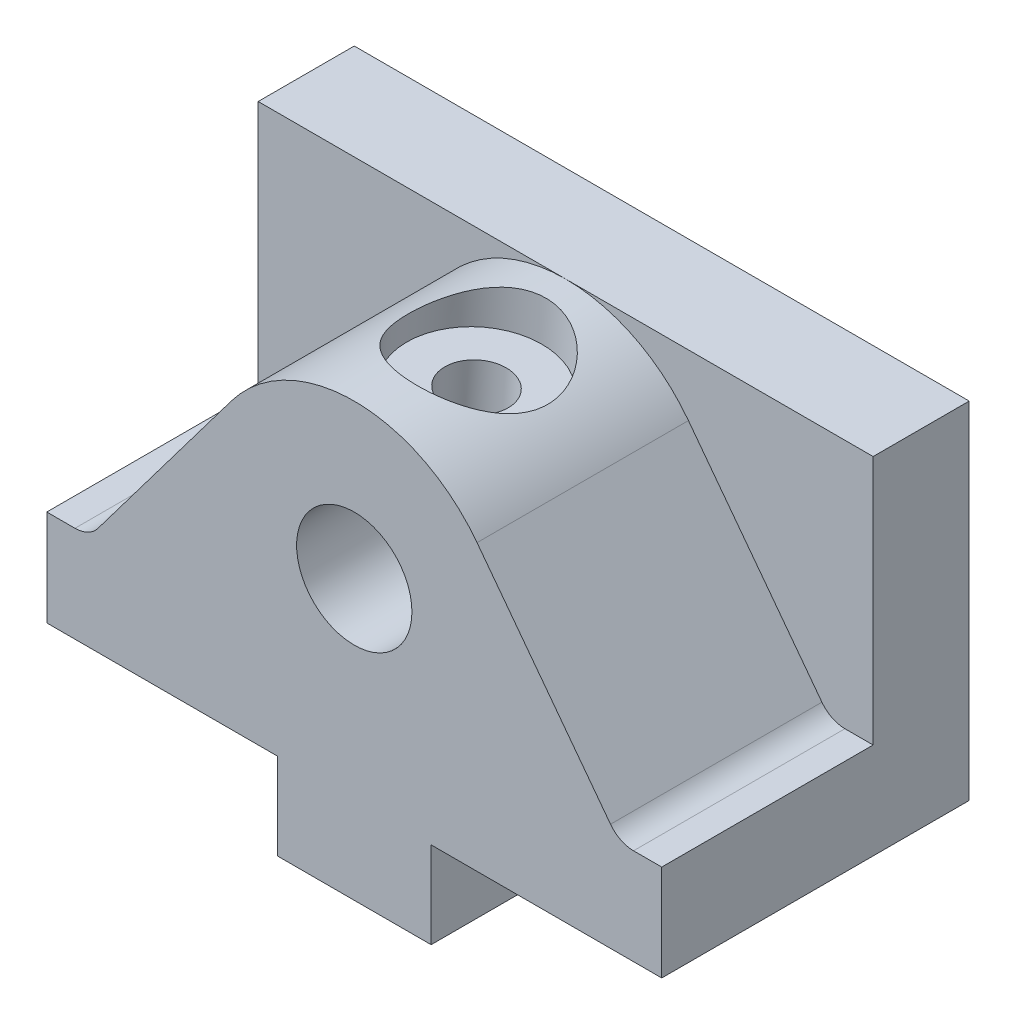
SolidWorks part; units mm, degrees
ref_plane "Front Plane" through (0, 0, 0) normal (0, 0, 1) x (1, 0, 0)
ref_plane "Top Plane" through (0, 0, 0) normal (0, 1, 0) x (1, 0, 0)
ref_plane "Right Plane" through (0, 0, 0) normal (1, 0, 0) x (0, 0, -1)
sketch "Sketch8" plane through (0, 0, 0) normal (0, 0, 1) x (1, 0, 0)
  line L0 (-54.603, 23.929) -> (-38.603, 23.929)
  line L1 (-38.603, 23.929) -> (-38.603, 32.929)
  line L2 (-38.603, 32.929) -> (-14.603, 32.929)
  line L3 (-14.603, 32.929) -> (-14.603, 68.929)
  line L4 (-14.603, 68.929) -> (-78.603, 68.929)
  line L5 (-78.603, 68.929) -> (-78.603, 32.929)
  line L6 (-78.603, 32.929) -> (-54.603, 32.929)
  line L7 (-54.603, 32.929) -> (-54.603, 23.929)
  dimension "D1" = 36
  dimension "D2" = 64
  dimension "D3" = 24
  dimension "D4" = 16
  dimension "D5" = 36
  dimension "D6" = 24
  dimension "D7" = 9
  dimension "D8" = 9
extrude "Extrude6" add sketch "Sketch8" against normal blind 32 contours L6 L7 L0 L1 L2 L3 L4 L5 region at (-46.603, 49.6055, 0)
sketch "Sketch9" plane through (0, 0, 0) normal (0, 0, 1) x (1, 0, 0)
  line L0 (-46.603, 79.5152) -> (-46.603, 21.0796) construction
  line L1 (-14.603, 68.929) -> (-78.603, 68.929) construction
  line L2 (-59.3812, 62.558) -> (-73.2726, 44.1236)
  line L3 (-33.8249, 62.558) -> (-19.9335, 44.1236)
  line L4 (-14.603, 32.929) -> (-14.603, 42.929) construction
  line L5 (-14.603, 32.929) -> (-14.603, 68.929) construction
  line L6 (-14.603, 42.929) -> (-17.5376, 42.929)
  line L7 (-75.6685, 42.929) -> (-78.603, 42.929)
  line L8 (-78.603, 68.929) -> (-78.603, 32.929) construction
  line L9 (-78.603, 68.929) -> (-14.603, 68.929)
  line L10 (-14.603, 68.929) -> (-14.603, 42.929)
  line L11 (-78.603, 68.929) -> (-78.603, 42.929)
  circle A0 centre (-46.603, 52.929) radius 6
  arc A1 (-33.8249, 62.558) -> (-59.3812, 62.558) centre (-46.603, 52.929) ccw
  arc A2 (-75.6685, 42.929) -> (-73.2726, 44.1236) centre (-75.6685, 45.929) ccw
  arc A3 (-17.5376, 42.929) -> (-19.9335, 44.1236) centre (-17.5376, 45.929) cw
  point P24 (-19.0333, 42.929)
  line M6 (-14.603, 32.929) -> (-14.603, 68.929)
  line M7 (-14.603, 68.929) -> (-78.603, 68.929)
  line M8 (-78.603, 68.929) -> (-78.603, 32.929)
  dimension "D2" = 16
  dimension "D3" = 37
  dimension "D4" = 32
  dimension "D7" = 3
  dimension "D1" = 37
  dimension "D5" = 10
  dimension "D6" = 10
extrude "Extrude13" cut sketch "Sketch9" against normal blind 22 contours L7 A2 L2 A1 L9 M8 | A3 L6 A1 L3 M6 M7 region at (-23.2448, 59.1383, 0) region at (-69.9613, 59.1383, 0)
sketch "Sketch12" plane through (0, 0, 0) normal (0, 0, 1) x (1, 0, 0)
  line L0 (-46.603, 74.3897) -> (-46.603, 19.3897) construction
  circle A0 centre (-46.603, 52.929) radius 6
  dimension "D1" = 16
extrude "Extrude14" cut sketch "Sketch12" against normal blind 22
hole_wizard "Ø6.0 (6) Diameter Hole1" positions "3DSketch1" profile "Sketch13" hole size "Ø6.0" standard "Ansi Metric"
sketch3d "3DSketch1"
  line L0 (-38.603, 23.929, -32) -> (-38.603, 23.929, 0) construction
  line L1 (-54.603, 23.929, 0) -> (-38.603, 23.929, 0) construction
  point P0 (-46.603, 23.929, -8)
  point P2 (-46.603, 23.929, -24)
  dimension "D1" = 8
  dimension "D2" = 16
  dimension "D3" = 8
  dimension "D4" = 8
sketch "Sketch13" plane through (-46.603, 23.929, -8) normal (1, 0, 0) x (0, 0, -1)
  line L0 (0, 0) -> (0, 17.8026)
  line L1 (0, 17.8026) -> (3, 16)
  line L2 (3, 16) -> (3, 0)
  line L5 (3, 0) -> (0, 0)
  line L10 (0, 17.8026) -> (-3, 16) construction
  line L11 (0, -6.35) -> (0, 107.95) construction
  dimension "Hole Dia." = 6
  dimension "Hole Depth" = 16
  dimension "Drill Angle" = 118
hole_wizard "CBORE for M6 Hex Head Bolt1" positions "3DSketch3" profile "Sketch15" counterbore size "M6" standard "Ansi Metric" end condition up to next
sketch3d "3DSketch3"
  line L0 (-14.603, 68.929, -32) -> (-78.603, 68.929, -32) construction
  point P0 (-45.6106, 68.8982, -12)
  dimension "D1" = 20
sketch "Sketch15" plane through (-45.6106, 68.8982, -12) normal (0, 0, 1) x (-0.9981, 0.062, 0)
  line L0 (0, 0) -> (0, 10)
  line L1 (0, 10) -> (3.3, 10)
  line L3 (3.3, 10) -> (3.3, 4.38)
  line L4 (3.3, 4.38) -> (7.275, 4.38)
  line L5 (7.275, 4.38) -> (7.275, 0)
  line L7 (7.275, 0) -> (0, 0)
  line L11 (0, -6.35) -> (0, 107.95) construction
  dimension "Thru Hole Dia." = 6.6
  dimension "Thru Hole Depth" = 10
  dimension "C'Bore Dia." = 14.55
  dimension "C'Bore Depth" = 4.38
